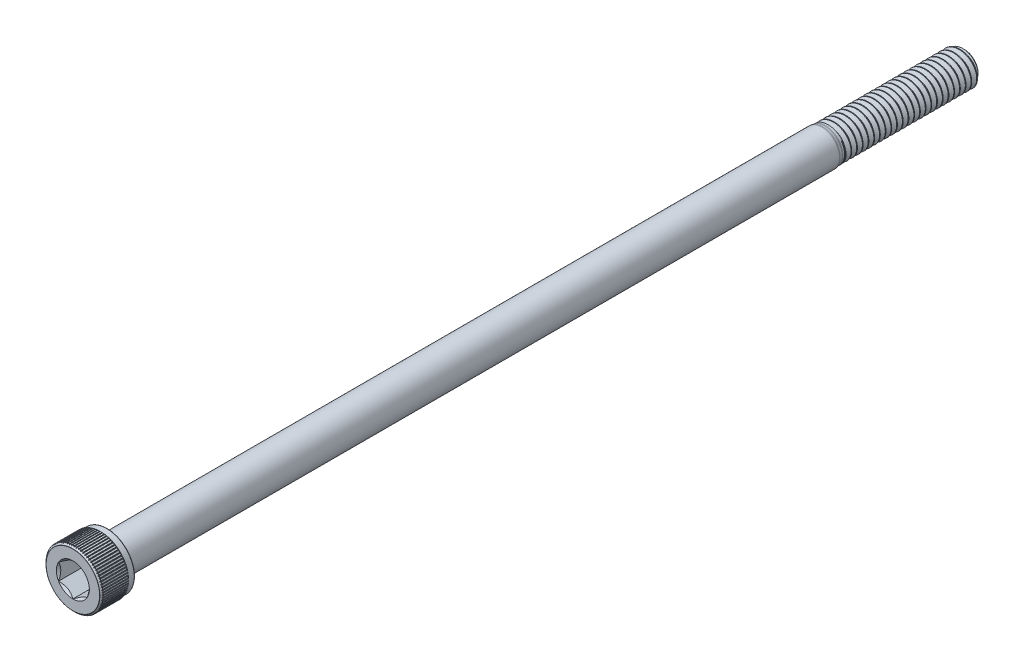
SolidWorks part; units mm, degrees
ref_plane "Front Plane" through (0, 0, 0) normal (0, 0, 1) x (1, 0, 0)
ref_plane "Top Plane" through (0, 0, 0) normal (0, 1, 0) x (1, 0, 0)
ref_plane "Right Plane" through (0, 0, 0) normal (1, 0, 0) x (0, 0, -1)
sketch "Sketch1" plane through (0, 0, 0) normal (1, 0, 0) x (0, 0, -1)
  line L0 (-78, 0) -> (78, 0) construction
  line L1 (78, 0) -> (78, 2.3505) construction
  line L2 (78, 2.3505) -> (77.3505, 3) construction
  line L3 (77.3505, 3) -> (77.25, 3) construction
  line L4 (77.25, 3) -> (-72, 3) construction
  line L5 (-72, 3) -> (-72, 5) construction
  line L6 (-72, 5) -> (-78, 5) construction
  line L7 (-78, 5) -> (-78, 0) construction
  line L8 (78, 2.3505) -> (78, 3) construction
  line L9 (77.9375, 3.1083) -> (78.4375, 2.2422) construction
  line L10 (78.4375, 2.2422) -> (78.9375, 3.1083) construction
  line L11 (78.9375, 3.1083) -> (77.9375, 3.1083) construction
  line L12 (78.4375, 3.1083) -> (78.4375, 3) construction
  line L13 (78.4375, 2.2422) -> (78.4375, 2.3505) construction
  line L14 (78.375, 2.3505) -> (78.5, 2.3505) construction
  line L15 (78, 3) -> (78.875, 3) construction
  line L16 (77.9687, 3.0541) -> (78.9062, 3.0541) construction
  line L17 (78, 0) -> (78, -3) construction
  line L18 (-72.3, 5) -> (-72, 4.7) construction
  line L19 (-77.7, 5) -> (-78, 4.7) construction
  line L20 (-72, 3) -> (-72, 0) construction
  line L21 (-72, 1.5) -> (-22, 1.5) construction
  line L22 (-22, 1.5) -> (28, 1.5) construction
  line L23 (28, 1.5) -> (78, 1.5) construction
  line L24 (-22, 1.5) -> (-22, 3) construction
  line L25 (-22, 3) -> (-22, 5) construction
  line L26 (28, 1.5) -> (28, 5) construction
  point P0 (-78, 2.5)
  point P3 (75.5, 3)
  point P4 (0, 0)
  point P18 (28, 3)
  point P22 (78.4375, 2.3505)
  point P24 (77.25, 3)
  point P25 (78.4375, 3)
  point P28 (78.4375, 3.0541)
  point P29 (75.5, -3)
  point P30 (-22, 3)
  point P31 (-75, 5)
  point P37 (-73.05, 5)
  point P38 (-77.55, 5)
  point P45 (-22, 1.5)
  point P46 (28, 1.5)
  point P49 (54, 3)
  dimension "D1" = 45
  dimension "D2" = 0.125
  dimension "D7" = 0.3
  dimension "D8" = 0.3
  dimension "D9" = 0.3
  dimension "D10" = 0.15
  dimension "D11" = 0.75
  dimension "Drive Size" = 5
  dimension "Head Diameter" = 10
  dimension "Head Height" = 6
  dimension "Thread Pitch" = 1
  dimension "Thread Dia" = 6
  dimension "Length" = 150
  dimension "D12" = 0.75
  dimension "D4" = 2.5
  dimension "Minimum Thread Length" = 24
sketch "Sketch2" plane through (0, 0, 0) normal (1, 0, 0) x (0, 0, -1)
  line L0 (-78, 0) -> (-78, 4.6689)
  line L1 (-77.6689, 5) -> (-73.3061, 5)
  line L2 (-72, 4.725) -> (-72, 3.4083)
  line L4 (77.3505, 3) -> (78, 2.3505)
  line L5 (78, 2.3505) -> (78, 0)
  line L6 (-72, 5) -> (-78, 5) construction
  line L7 (78, 0) -> (-78, 0)
  line L8 (-77.7, 5) -> (-78, 4.7) construction
  line L10 (-77.722, 4.978) -> (-77.978, 4.722)
  line L12 (-73.0939, 4.85) -> (-72.125, 4.85)
  line L14 (-72.3, 5) -> (-72, 4.7) construction
  line L15 (-73.253, 4.978) -> (-73.147, 4.872)
  line L17 (-72, 3) -> (-72, 5) construction
  line L18 (-71.7, 3.1083) -> (53.0069, 3.1083)
  line L19 (53.6989, 3) -> (77.3505, 3)
  line L20 (77.25, 3) -> (-72, 3) construction
  line L21 (53.1532, 3.0938) -> (53.5526, 3.0144)
  line L22 (78.9375, 3.1083) -> (77.9375, 3.1083) construction
  arc A0 (-72.125, 4.85) -> (-72, 4.725) centre (-72.125, 4.725) cw
  arc A1 (-72, 3.4083) -> (-71.7, 3.1083) centre (-71.7, 3.4083) ccw
  arc A2 (53.0069, 3.1083) -> (53.1532, 3.0938) centre (53.0069, 2.3583) cw
  arc A3 (53.5526, 3.0144) -> (53.6989, 3) centre (53.6989, 3.75) ccw
  arc A4 (-77.722, 4.978) -> (-77.6689, 5) centre (-77.6689, 4.925) cw
  arc A5 (-77.978, 4.722) -> (-78, 4.6689) centre (-77.925, 4.6689) ccw
  arc A6 (-73.253, 4.978) -> (-73.3061, 5) centre (-73.3061, 4.925) ccw
  arc A7 (-73.147, 4.872) -> (-73.0939, 4.85) centre (-73.0939, 4.925) ccw
  point P22 (-72.15, 4.85)
  point P39 (53.625, 3)
  point P47 (-73.125, 4.85)
  dimension "D2" = 0.125
  dimension "D3" = 0.3
  dimension "D6" = 0.75
  dimension "D7" = 0.075
  dimension "D1" = 1.125
  dimension "D4" = 11.25
  dimension "D5" = 0.375
  dimension "D8" = 124.7069
revolve "Revolve1" add sketch "Sketch2" angle 360 about L7
sketch "Sketch3" plane through (0, 0, 78) normal (0, 0, 1) x (1, 0, 0)
  line L1 (2.5, -1.4434) -> (2.5, 1.4434)
  line L2 (2.5, 1.4434) -> (0, 2.8868)
  line L3 (0, 2.8868) -> (-2.5, 1.4434)
  line L4 (-2.5, 1.4434) -> (-2.5, -1.4434)
  line L5 (-2.5, -1.4434) -> (0, -2.8868)
  line L6 (0, -2.8868) -> (2.5, -1.4434)
  circle A0 centre (0, 0) radius 2.5 construction
  circle A1 centre (0, 0) radius 5 construction
  circle A2 centre (0, 0) radius 5 construction
extrude "Cut-Extrude1" cut sketch "Sketch3" against normal offset from surface (5 mm away) 1 up to face at (-4.725, 0, 72)
sketch "Sketch4" plane through (0, 0, 78) normal (0, 0, 1) x (1, 0, 0)
  circle A0 centre (0, 0) radius 2.8868
extrude "Cut-Extrude2" cut sketch "Sketch4" against normal up to vertex (3 mm away) draft 45 up to point (0, 5, 75)
sketch "Sketch11" plane through (0, 0, 0) normal (1, 0, 0) x (0, 0, -1)
  line L0 (-78, 0) -> (78, 0) construction
  line L1 (-78, 0) -> (78, 0) construction
  line L2 (29.6244, -3) -> (29.6244, 3) construction
  line L3 (77.25, 3) -> (-72, 3) construction
  line L4 (-40.8233, -3) -> (-40.8233, 3) construction
  line L5 (53.0069, 3.1083) -> (53.0069, -3.1083) construction
  point P7 (29.6244, 0)
  point P10 (-40.8233, 0)
  dimension "D1" = 31.1767
  dimension "D2" = 23.3825
sketch "Sketch6" plane through (0, 0, -78) normal (0, 0, -1) x (-1, 0, 0)
  circle A0 centre (0, 0) radius 3
curve "Helix/Spiral1" pitch 1 height 25 radius 3 centre (0, 0, -78) axis (0, 0, 1) start towards (0, 1, 0)
sketch "Sketch10" plane through (0, 0, 0) normal (1, 0, 0) x (0, 0, -1)
  line L0 (54, -3) -> (54, 3)
  line L2 (-78, 0) -> (78, 0) construction
  point P3 (54, 0)
split "Split1" trim tools "Sketch10" bodies to split 106 resulting bodies 114 115
sketch "Sketch7" plane through (0, 0, 0) normal (1, 0, 0) x (0, 0, -1)
  line L0 (77.9687, 3.0541) -> (78.9062, 3.0541)
  line L1 (78.9062, 3.0541) -> (78.5, 2.3505)
  line L2 (78.5, 2.3505) -> (78.375, 2.3505)
  line L3 (78.375, 2.3505) -> (77.9687, 3.0541)
sweep "Cut-Sweep1" cut profiles "Sketch7" path "Helix/Spiral1" align with end faces yes
sketch "Sketch8" plane through (0, 0, 0) normal (1, 0, 0) x (0, 0, -1)
  line L0 (-72, 0) -> (-72, 3)
  line L2 (-72, 3) -> (54, 3)
  line L4 (54, 3) -> (55.7321, 0)
  line L5 (55.7321, 0) -> (-72, 0)
  line L6 (77.25, 3) -> (-72, 3) construction
  line L7 (-78, 0) -> (78, 0) construction
  dimension "D1" = 60
  dimension "D2" = 24
revolve "Revolve2" add sketch "Sketch8" angle 360 about L5
sketch "Sketch9" plane through (0, 0, 78) normal (0, 0, 1) x (1, 0, 0)
  line L0 (-0.0228, 4.9009) -> (-0.125, 5.1291)
  line L1 (-0.125, 5.1291) -> (0.125, 5.1291)
  line L2 (0.125, 5.1291) -> (0.0228, 4.9009)
  line L3 (0, 5) -> (0, 4.7) construction
  line L4 (0, 0) -> (-0.125, 5.1291) construction
  line L5 (0.125, 5.1291) -> (0, 0) construction
  circle A0 centre (0, 0) radius 4.85 construction
  arc A4 (-0.0228, 4.9009) -> (0.0228, 4.9009) centre (0, 4.9112) ccw
  point P10 (0, 4.85)
  point P19 (0, 4.85)
  dimension "D2" = 0.025
  dimension "D1" = 0.25
  dimension "D3" = 2.792
extrude "Cut-Extrude3" cut sketch "Sketch9" against normal through all
pattern_circular "CirPattern1" count 80 over 360 about axis through (0, 0, 77.6689) along (0, 0, -1) of "Cut-Extrude3"
equation "\"D2@Sketch1\" = \"Thread Pitch@Sketch1\" / 8"
equation "\"D4@Helix/Spiral1\" = \"Thread Pitch@Sketch1\""
equation "\"D7@Sketch1\" = \"Head Height@Sketch1\" * .05"
equation "\"D8@Sketch1\"=\"D7@Sketch1\""
equation "\"D9@Sketch1\"=\"D7@Sketch1\""
equation "\"D10@Sketch1\"=\"D7@Sketch1\"/2"
equation "\"D11@Sketch1\"=\"D10@Sketch1\"*5"
equation "\"D4@Sketch1\"=\"Thread Pitch@Sketch1\"*2.5"
equation "\"D12@Sketch1\"=\"Thread Pitch@Sketch1\"*.75"
equation "\"D3@Helix/Spiral1\"=\"Minimum Thread Length@Sketch1\"+\"Thread Pitch@Sketch1\""
equation "\"D2@Sketch8\"=\"Minimum Thread Length@Sketch1\""
equation "\"D1@Sketch2\"=\"Head Height@Sketch1\"*0.1875"
equation "\"D2@Sketch2\"=\"Head Diameter@Sketch1\"*0.0125"
equation "\"D3@Sketch2\"=\"Thread Dia@Sketch1\"*0.05"
equation "\"D1@Sketch9\"=\"Head Diameter@Sketch1\"*0.025"
equation "\"D2@Sketch9\"=\"D1@Sketch9\"*0.1"
equation "\"D1@CirPattern1\"=int ((360/\"D3@Sketch9\")*0.625)"
equation "\"D5@Sketch2\"=\"D12@Sketch1\"*0.5"
equation "\"D6@Sketch2\"=\"Thread Dia@Sketch1\"*0.125"
equation "\"D7@Sketch2\"=\"D8@Sketch1\"*0.25"
equation "\"D1@Sketch11\"=\"D8@Sketch2\"*0.25"
equation "\"D2@Sketch11\"=\"D8@Sketch2\"*0.1875"
